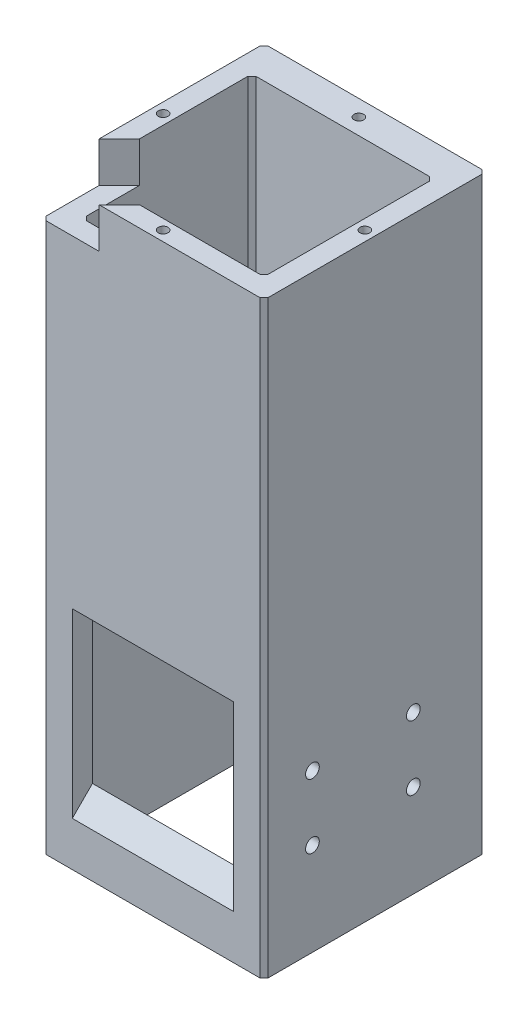
SolidWorks part; units mm, degrees
material "Custom Plastic"
ref_plane "Front Plane" through (0, 0, 0) normal (0, 0, 1) x (1, 0, 0)
ref_plane "Top Plane" through (0, 0, 0) normal (0, 1, 0) x (1, 0, 0)
ref_plane "Right Plane" through (0, 0, 0) normal (1, 0, 0) x (0, 0, -1)
sketch "Sketch1" plane through (0, 0, 0) normal (0, 1, 0) x (1, 0, 0)
  line L0 (-22.5, 22.5) -> (-22.5, -22.5)
  line L1 (27.5, -27.5) -> (27.5, 27.5)
  line L2 (27.5, -27.5) -> (-27.5, -27.5)
  line L3 (-27.5, -27.5) -> (-27.5, 27.5)
  line L4 (27.5, 27.5) -> (-27.5, 27.5)
  line L5 (27.5, -27.5) -> (-27.5, 27.5) construction
  line L6 (-27.5, -27.5) -> (27.5, 27.5) construction
  line L7 (-22.5, 22.5) -> (22.5, 22.5)
  line L8 (22.5, 22.5) -> (22.5, -22.5)
  line L9 (-22.5, -22.5) -> (22.5, -22.5)
  line L10 (-22.5, 22.5) -> (22.5, -22.5) construction
  line L11 (22.5, 22.5) -> (-22.5, -22.5) construction
  line L12 (-22.5, 19.5) -> (22.5068, 19.5)
  point P0 (0, 0)
  point P21 (0, 0)
  dimension "D1" = 8
  dimension "D3" = 45
  dimension "D4" = 5
extrude "Boss-Extrude1" add sketch "Sketch1" along normal blind 130 and the other way blind 16 contours L1 L4 L3 L2 L9 L0 L7 L8 | L0 L12 L8 L7 region at (0, 0, -21) region at (0, 0, 26.7222)
sketch "Sketch2" plane through (0, 0, 27.5) normal (0, 0, 1) x (1, 0, 0)
  line L1 (-20, 35) -> (20, 35)
  line L2 (-20, 35) -> (-20, 0)
  line L3 (-20, 0) -> (20, 0)
  line L4 (20, 35) -> (20, 0)
  line L5 (-20, 35) -> (20, 0) construction
  line L6 (-20, 0) -> (20, 35) construction
  line L9 (27.5, -16) -> (-27.5, -16) construction
  point P0 (0, 11.0595)
  point P8 (0, -16)
  dimension "D1" = 40
  dimension "D2" = 51
  dimension "D3" = 35
extrude "Cut-Extrude1" cut sketch "Sketch2" against normal blind 168
sketch "Sketch7" plane through (0, 0, -27.5) normal (0, 0, -1) x (-1, 0, 0)
  line L1 (22.5, 44.7) -> (22.5, 78.7)
  line L2 (19.5, 81.7) -> (-19.5, 81.7)
  line L3 (-22.5, 78.7) -> (-22.5, 44.7)
  line L8 (22.5, 78.7) -> (19.5, 81.7)
  line L10 (19.5, 41.7) -> (-19.5, 41.7)
  line L11 (-19.5, 81.7) -> (-22.5, 78.7)
  line L12 (22.5, 44.7) -> (19.5, 41.7)
  line L13 (-22.5, 44.7) -> (-19.5, 41.7)
  line L14 (-27.5, 130) -> (27.5, 130) construction
  point P0 (0, 130)
  point P1 (22.5, 41.7)
  point P2 (-22.5, 81.7)
  point P3 (22.5, 81.7)
  point P4 (-22.5, 41.7)
  point P9 (0, 81.7)
  dimension "D1" = 48.3
  dimension "D3" = 40
  dimension "D4" = 45
extrude "Cut-Extrude2" cut sketch "Sketch7" against normal blind 10 contours L12 L1 L8 | L13 L10 L12 L8 L2 L11 | L3 L13 L11 region at (0, 61.7, -27.5)
sketch "Sketch8" plane through (0, 81.7, 0) normal (0, -1, 0) x (1, 0, 0)
  line L0 (-12.5, -27.5) -> (-12.5, -19.5)
  line L1 (12.5, -19.5) -> (12.5, -27.5)
  line L2 (-22.5, -19.5) -> (22.5, -19.5) construction
  line L3 (-19.5, -27.5) -> (19.5, -27.5) construction
  line L5 (-12.5, -19.5) -> (12.5, -19.5)
  line L6 (12.5, -27.5) -> (-12.5, -27.5)
  point P2 (0, -27.5)
  point P14 (0, -27.5)
  dimension "D1" = 25
extrude "Cut-Extrude5" cut sketch "Sketch8" against normal blind 5
hole_wizard "CSK for M2 Flat Head Machine Screw2" positions "Sketch9" profile "Sketch10" countersink size "M2" standard "ANSI Metric"
sketch "Sketch9" plane through (0, 86.7, 0) normal (0, -1, 0) x (-1, 0, 0)
  line L0 (12.5, 27.5) -> (-12.5, 27.5) construction
  line L1 (-12.5, 27.5) -> (-12.5, 19.5) construction
  line L2 (12.5, 19.5) -> (12.5, 27.5) construction
  point P0 (-5.5, 23.5)
  point P2 (5.5, 23.5)
  dimension "D1" = 4
  dimension "D2" = 7
  dimension "D3" = 7
sketch "Sketch10" plane through (5.5, 86.7, -23.5) normal (1, 0, 0) x (0, 0, -1)
  line L0 (0, 0) -> (0, 10)
  line L1 (0, 10) -> (1.2, 9.279)
  line L2 (1.2, 9.279) -> (1.2, 1)
  line L3 (1.2, 1) -> (2.2, 0)
  line L5 (2.2, 0) -> (0, 0)
  line L6 (-1.2, 1) -> (-2.2, 0) construction
  line L10 (0, 10) -> (-1.2, 9.279) construction
  line L11 (0, -6.35) -> (0, 107.95) construction
  dimension "Hole Dia." = 2.4
  dimension "Hole Depth" = 10
  dimension "Near C'Sink Dia." = 4.4
  dimension "Near C'Sink Angle" = 90
  dimension "Drill Angle" = 118
chamfer "Chamfer1" distance 1 angle 45 6 edges at (22.5, 57, 22.5) (-22.5, 57, 22.5) (22.5, 14.35, -19.5) (-22.5, 14.35, -19.5) (22.5, 104.35, -19.5) (-22.5, 104.35, -19.5)
chamfer "Chamfer3" distance 1 angle 45 4 edges at (27.5, 57, -27.5) (27.5, 57, 27.5) (-27.5, 57, -27.5) (-27.5, 57, 27.5)
ref_plane "Plane1" through (-27, 0, 27) normal (-0.7071, 0, 0.7071) x (0.7071, 0, 0.7071)
sketch "Sketch11" plane through (-27, 0, 27) normal (-0.7071, 0, 0.7071) x (0.7071, 0, 0.7071)
  line L1 (-10, 120) -> (10, 120)
  line L2 (-10, 120) -> (-10, 130)
  line L3 (-10, 130) -> (10, 130)
  line L4 (10, 120) -> (10, 130)
  point P6 (10, 125)
  point P7 (10, 125)
  dimension "D1" = 20
  dimension "D2" = 10
extrude "Cut-Extrude6" cut sketch "Sketch11" against normal up to next
sketch "Sketch12" plane through (27.5, 0, 0) normal (1, 0, 0) x (0, 0, -1)
  line L0 (9.5, 7) -> (-15.5, 7) construction
  line L1 (9.5, 7) -> (9.5, 23) construction
  line L3 (-26.5, -16) -> (26.5, -16) construction
  circle A0 centre (9.5, 7) radius 1.7
  circle A1 centre (-15.5, 7) radius 1.7
  circle A2 centre (-15.5, 23) radius 1.7
  circle A3 centre (9.5, 23) radius 1.7
  point P6 (0, -16)
  dimension "D3" = 3.4
  dimension "D1" = 16
  dimension "D2" = 25
  dimension "D4" = 23
extrude "Cut-Extrude7" cut sketch "Sketch12" against normal up to next
chamfer "Chamfer2" distance 5 angle 45 4 edges at (0, 0, -27.5) (0, 35, -27.5) (0, 35, 27.5) (0, 0, 27.5)
sketch "Sketch13" plane through (0, 130, 0) normal (0, 1, 0) x (1, 0, 0)
  line L0 (0, 23.5) -> (0, -25) construction
  line L1 (-25, 0) -> (25, 0) construction
  line L2 (12.3407, -22.5) -> (12.3407, -27.5) construction
  line L3 (22.5, -10.5594) -> (27.5, -10.5594) construction
  line L8 (26.5, -27.5) -> (-13.3579, -27.5) construction
  line L9 (-8.3579, -22.5) -> (21.5, -22.5) construction
  line L10 (22.5, 18.5) -> (22.5, -21.5) construction
  line L11 (27.5, -26.5) -> (27.5, 26.5) construction
  line L13 (-7.7348, 27.5) -> (-7.7348, 19.5) construction
  line L14 (26.5, 27.5) -> (-26.5, 27.5) construction
  line L15 (-21.5, 19.5) -> (21.5, 19.5) construction
  circle A0 centre (0, 23.5) radius 1.2
  circle A1 centre (0, -25) radius 1.2
  circle A2 centre (25, 0) radius 1.2
  circle A3 centre (-25, 0) radius 1.2
  point P25 (12.3407, -25)
  point P27 (25, -10.5594)
  point P31 (0, 0)
  point P33 (-7.7348, 23.5)
  dimension "D1" = 2.4
extrude "Cut-Extrude8" cut sketch "Sketch13" against normal blind 10
